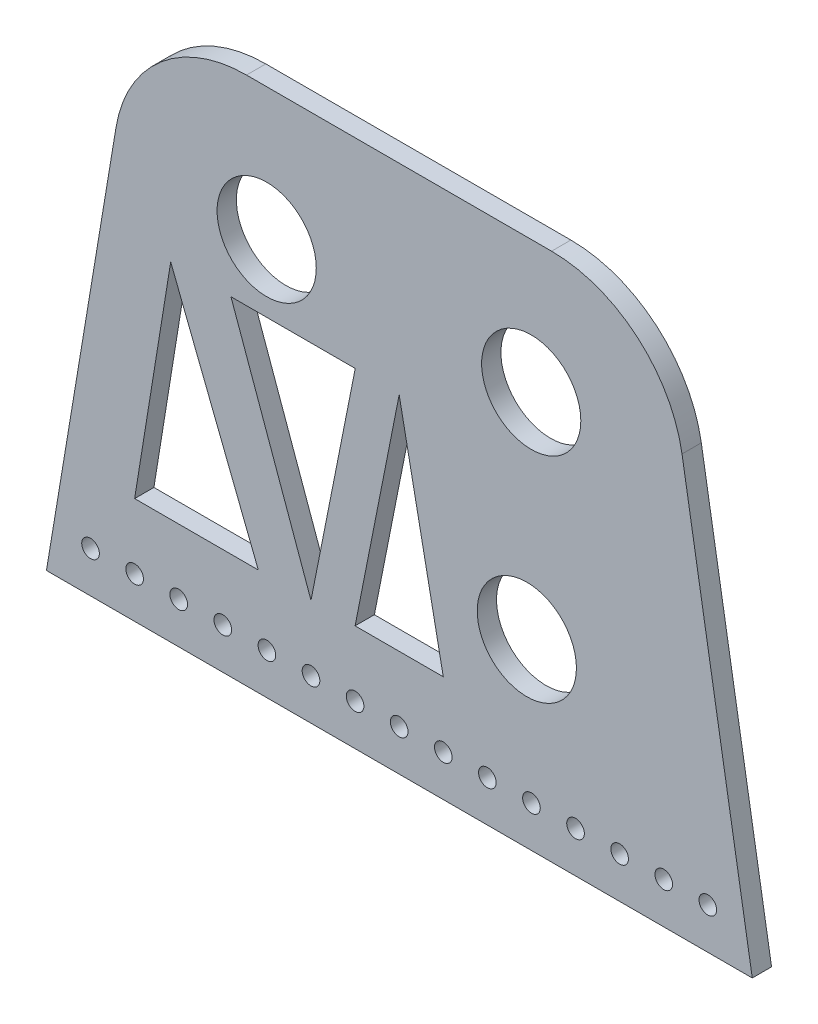
SolidWorks part; units mm, degrees
ref_plane "Front Plane" through (0, 0, 0) normal (0, 0, 1) x (1, 0, 0)
ref_plane "Top Plane" through (0, 0, 0) normal (0, 1, 0) x (1, 0, 0)
ref_plane "Right Plane" through (0, 0, 0) normal (1, 0, 0) x (0, 0, -1)
sketch "Sketch2" plane through (0, 0, 0) normal (0, 0, 1) x (1, 0, 0)
  line L0 (-33.222, -123.0337) -> (-58.5557, -123.0337)
  line L1 (-33.222, 29.3663) -> (119.178, 29.3663)
  line L3 (-33.222, -123.0337) -> (119.178, -123.0337)
  line L5 (-58.5557, -123.0337) -> (-33.222, 29.3663)
  line L6 (119.178, -123.0337) -> (144.7459, -123.0337)
  line L7 (144.7459, -123.0337) -> (119.178, 29.3663)
  line L8 (-22.7678, -28.1678) -> (-33.1557, -92.3946)
  line L9 (-33.1557, -92.3946) -> (2.468, -92.3946)
  line L10 (2.468, -92.3946) -> (-22.7678, -28.1678)
  line L14 (43.0443, -28.3997) -> (55.7443, -92.3946)
  line L15 (55.7443, -92.3946) -> (30.3443, -92.3946)
  line L16 (30.3443, -92.3946) -> (43.0443, -28.3997)
  line L20 (17.6443, -92.3946) -> (30.3903, -28.1678)
  line L21 (30.3903, -28.1678) -> (-5.4154, -28.1678)
  line L22 (-5.4154, -28.1678) -> (17.6443, -92.3946)
  circle A0 centre (4.878, -8.7337) radius 14.2875
  circle A1 centre (81.078, -8.7337) radius 14.2875
  circle A2 centre (-45.8557, -111.1877) radius 2.54
  circle A3 centre (-33.1557, -111.1877) radius 2.54
  circle A4 centre (-20.4557, -111.1877) radius 2.54
  circle A5 centre (-7.7557, -111.1877) radius 2.54
  circle A6 centre (4.9443, -111.1877) radius 2.54
  circle A7 centre (17.6443, -111.1877) radius 2.54
  circle A8 centre (30.3443, -111.1877) radius 2.54
  circle A9 centre (43.0443, -111.1877) radius 2.54
  circle A10 centre (55.7443, -111.1877) radius 2.54
  circle A11 centre (68.4443, -111.1877) radius 2.54
  circle A12 centre (81.1443, -111.1877) radius 2.54
  circle A13 centre (93.8443, -111.1877) radius 2.54
  circle A14 centre (106.5443, -111.1877) radius 2.54
  circle A15 centre (119.2443, -111.1877) radius 2.54
  circle A16 centre (131.9443, -111.1877) radius 2.54
  circle A17 centre (79.8095, -71.0514) radius 14.2875
  dimension "D3" = 28.575
  dimension "D4" = 28.575
  dimension "D9" = 15
  dimension "D10" = 12.7
  dimension "D11" = 28.575
  dimension "D1" = 152.4
  dimension "D2" = 152.4
  dimension "D5" = 76.2
  dimension "D6" = 38.1
  dimension "D7" = 38.1
  dimension "D8" = 38.1
extrude "Boss-Extrude1" add sketch "Sketch2" along normal blind 5.5562
fillet "Fillet1" radius 38.1 2 edges at (-33.222, 29.3663, 2.7781) (119.178, 29.3663, 2.7781)
